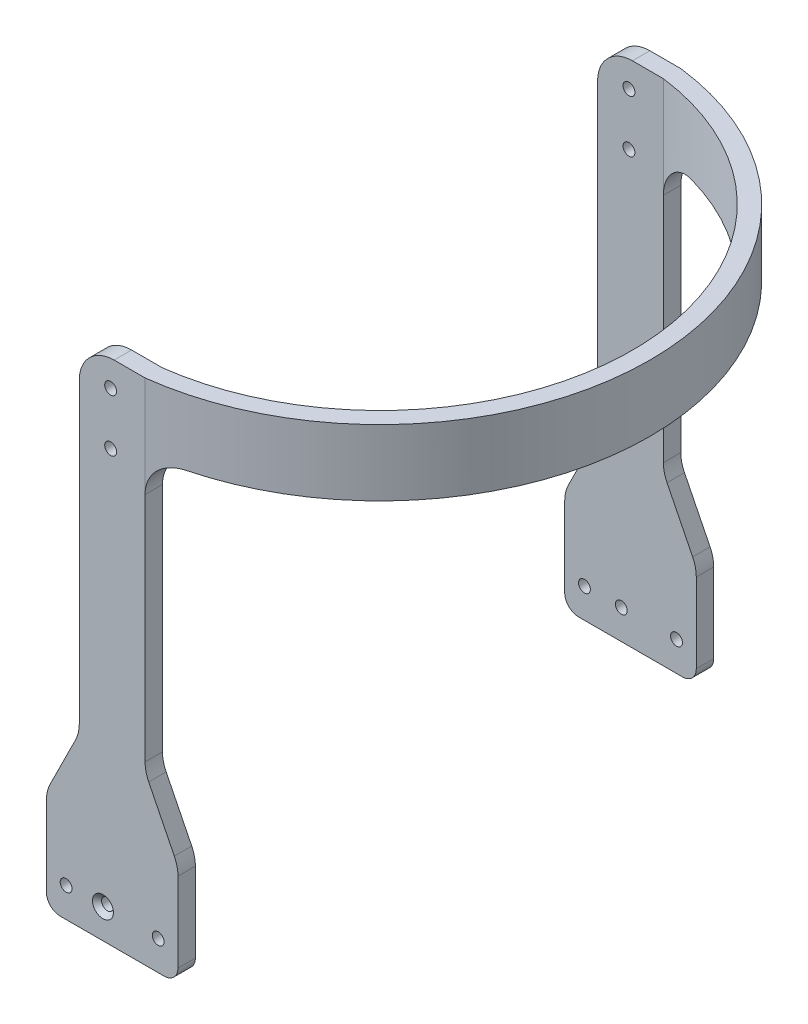
SolidWorks part; units mm, degrees
material "1060 Alloy"
ref_plane "Front Plane" through (0, 0, 0) normal (0, 0, 1) x (1, 0, 0)
ref_plane "Top Plane" through (0, 0, 0) normal (0, 1, 0) x (1, 0, 0)
ref_plane "Right Plane" through (0, 0, 0) normal (1, 0, 0) x (0, 0, -1)
sketch "Sketch1" plane through (0, 0, 0) normal (0, 0, 1) x (1, 0, 0)
  line L0 (0, 0) -> (37.75, 0)
  line L1 (37.75, 0) -> (37.75, 29.178)
  line L2 (37.75, 29.178) -> (28.3125, 48.144)
  line L3 (28.3125, 48.144) -> (28.3125, 145.891)
  line L4 (28.3125, 145.891) -> (9.4375, 145.891)
  line L5 (9.4375, 145.891) -> (9.4375, 48.144)
  line L6 (9.4375, 48.144) -> (0, 29.178)
  line L7 (0, 29.178) -> (0, 0)
  line L8 (5.6625, 8.494) -> (32.0875, 8.494) construction
  circle A0 centre (5.6625, 8.494) radius 1.7
  circle A1 centre (32.0875, 8.494) radius 1.7
  point P13 (18.875, 8.494)
  point P14 (18.875, 0)
  dimension "D8" = 3.4
  dimension "D1" = 29.178
  dimension "D2" = 48.144
  dimension "D3" = 145.891
  dimension "D4" = 26.425
  dimension "D5" = 37.75
  dimension "D6" = 8.494
  dimension "D7" = 18.875
extrude "Boss-Extrude3" add sketch "Sketch1" along normal blind 5
sketch "Sketch4" plane through (0, 145.891, 0) normal (0, 1, 0) x (1, 0, 0)
  line L0 (28.3125, 143.69) -> (28.3125, 148.69)
  line L2 (28.3125, -5) -> (28.3125, 0) construction
  line L3 (28.3125, -5) -> (28.3125, 0)
  line L5 (28.3125, 0) -> (9.4375, 0) construction
  line L6 (28.3125, 0) -> (9.4375, 0) construction
  arc A0 (28.3125, -5) -> (28.3125, 148.69) centre (18.875, 71.845) ccw
  arc A1 (28.3125, 0) -> (28.3125, 143.69) centre (18.875, 71.845) ccw
  point P11 (18.875, 0)
  dimension "D1" = 71.845
extrude "Boss-Extrude4" add sketch "Sketch4" against normal blind 18.966
ref_point "Point2"
ref_plane "Plane5" through (5.6625, 0, 0) normal (-1, 0, 0) x (0, 0, 1)
ref_plane "Plane4" through (16.2325, 0, 0) normal (-1, 0, 0) x (0, 0, 1)
sketch "Sketch5" plane through (16.2325, 0, 0) normal (-1, 0, 0) x (0, 0, 1)
  line L0 (2.5, 0) -> (2.5, 8.494) construction
  line L1 (5, 0) -> (0, 0) construction
  line L2 (5, 8.494) -> (0, 8.494)
  line L3 (5, 0) -> (5, 29.178) construction
  line L4 (0, 0) -> (0, 29.178) construction
  line L5 (5, 8.494) -> (5, 10.194)
  line L8 (0, 11.494) -> (0, 8.494)
  line L9 (-7.0315, 8.494) -> (14.5293, 8.494) construction
  line L10 (0, 11.494) -> (1.3, 10.194)
  line L11 (1.3, 10.194) -> (5, 10.194)
  line L12 (0, 29.178) -> (0, 0) construction
  dimension "D1" = 8.494
  dimension "D2" = 3.4
  dimension "D3" = 6
  dimension "D4" = 45
revolve "Cut-Revolve1" [suppressed] cut sketch "Sketch5" angle 360 about L9
ref_point "Point1"
ref_plane "Plane3" through (0, 0, -71.845) normal (0, 0, -1) x (-1, 0, 0)
sketch "Sketch6" plane through (0, 0, 5) normal (0, 0, 1) x (1, 0, 0)
  line L0 (18.4375, 138.391) -> (18.4375, 123.391) construction
  line L1 (28.3125, 136.408) -> (9.4375, 136.408) construction
  line L2 (28.3125, 126.925) -> (28.3125, 145.891) construction
  line L3 (9.4375, 145.891) -> (9.4375, 48.144) construction
  line L4 (28.3125, 145.891) -> (9.4375, 145.891) construction
  circle A0 centre (18.4375, 138.391) radius 1.7
  circle A1 centre (18.4375, 123.391) radius 1.7
  dimension "D1" = 3.4
  dimension "D2" = 7.5
  dimension "D3" = 15
  dimension "D4" = 9
extrude "Cut-Extrude1" cut sketch "Sketch6" against normal up to surface (5 mm away) up to face at (19.9236, 63.7057, 0)
mirror "Mirror2" about plane through (0, 0, -71.845) normal (0, 0, -1) of "Boss-Extrude3", "Cut-Extrude1"
fillet "Fillet1" radius 10 4 edges at (9.4375, 145.891, -146.19) (9.4375, 145.891, 2.5) (28.3125, 126.925, -146.19) (28.3125, 126.925, 2.5)
fillet "Fillet2" radius 10 8 edges at (28.3125, 48.144, 2.5) (37.75, 29.178, 2.5) (0, 29.178, 2.5) (9.4375, 48.144, 2.5) (0, 29.178, -146.19) (37.75, 29.178, -146.19) (28.3125, 48.144, -146.19) (9.4375, 48.144, -146.19)
fillet "Fillet3" radius 4 4 edges at (0, 0, -146.19) (37.75, 0, -146.19) (0, 0, 2.5) (37.75, 0, 2.5)
sketch "Sketch7" plane through (16.2325, 0, 0) normal (-1, 0, 0) x (0, 0, 1)
  line L0 (-125.8278, 8.494) -> (49874.1722, 8.494) construction
  line L1 (-148.69, 8.494) -> (-148.69, 11.494)
  line L2 (-148.69, 26.8275) -> (-148.69, 4) construction
  line L3 (-148.69, 11.494) -> (-147.39, 10.194)
  line L4 (-147.39, 10.194) -> (-143.69, 10.194)
  line L5 (-143.69, 26.8275) -> (-143.69, 4) construction
  line L6 (-143.69, 10.194) -> (-143.69, 8.494)
  line L7 (-143.69, 8.494) -> (-148.69, 8.494)
  line L8 (-143.69, 0) -> (-148.69, 0) construction
  dimension "D2" = 3.4
  dimension "D1" = 6
  dimension "D4" = 8.494
  dimension "D3" = 45
revolve "Cut-Revolve2" cut sketch "Sketch7" angle 360 about L0
mirror "Mirror3" about plane through (0, 0, -71.845) normal (0, 0, -1) of "Cut-Revolve2"
equation "\"B1\"=0.037750"
equation "\"B2\"=0.018875"
equation "\"B3\"=0.055704"
equation "\"H1\"=0.029178"
equation "\"H2\"=0.048144"
equation "\"H3\"=0.126925"
equation "\"H4\"=0.145891"
equation "\"T\"=0.005000"
equation "\"L\"=0.026425"
equation "\"bolt_hole_diameter\"=0.003400"
equation "\"D1@Sketch1\"=\"H1\"*1000"
equation "\"D2@Sketch1\"=\"H2\"*1000"
equation "\"D3@Sketch1\"=\"H4\"*1000"
equation "\"D4@Sketch1\"=\"L\"*1000"
equation "\"D5@Sketch1\"=\"B1\"*1000"
equation "\"D6@Sketch1\"=\"H_holes\"*1000"
equation "\"D7@Sketch1\"=\"B2\"*1000"
equation "\"D8@Sketch1\"=\"bolt_hole_diameter\"*1000"
equation "\"D1@Boss-Extrude3\"=\"T\"*1000"
equation "\"D1@Sketch4\"=\"D_strap\"*1000"
equation "\"D1@Boss-Extrude4\"=(\"H4\"-\"H3\")*1000"
equation "\"spring_arm_hole_pos\"=0.010570"
equation "\"spring_arm_hole_max_diam\"=0.006000"
equation "\"spring_arm_hole_min_diam\"=0.003400"
equation "\"arm_hole_head_height\"=0.001650"
equation "\"H_holes\"=0.008494"
equation "\"D1@Sketch5\"=\"H_holes\"*1000"
equation "\"D_strap\"=0.071845"
equation "\"clip_hole_D\"=0.003400"
equation "\"clip_hole_y1\"=0.007500"
equation "\"clip_hole_dist\"=0.015000"
equation "\"pad_t1\"=0.016141"
equation "\"pad_t2\"=0.000000"
equation "\"unpad_L1\"=0.067481"
equation "\"D1@Sketch6\"=\"clip_hole_D\"*1000"
equation "\"D2@Sketch6\"=\"clip_hole_y1\"*1000"
equation "\"D3@Sketch6\"=\"clip_hole_dist\"*1000"
equation "\"D1@Plane4\"=\"spring_arm_hole_pos\"*1000"
equation "\"D2@Sketch5\"=\"spring_arm_hole_min_diam\"*1000"
equation "\"D3@Sketch5\"=\"spring_arm_hole_max_diam\"*1000"
equation "\"D1@Sketch7\"=\"spring_arm_hole_max_diam\"*1000"
equation "\"D2@Sketch7\"=\"spring_arm_hole_min_diam\"*1000"
equation "\"D4@Sketch7\"=\"H_holes\"*1000"
equation "\"clip_hole_x\"=0.009"
equation "\"D4@Sketch6\"=\"clip_hole_x\"*1000"
